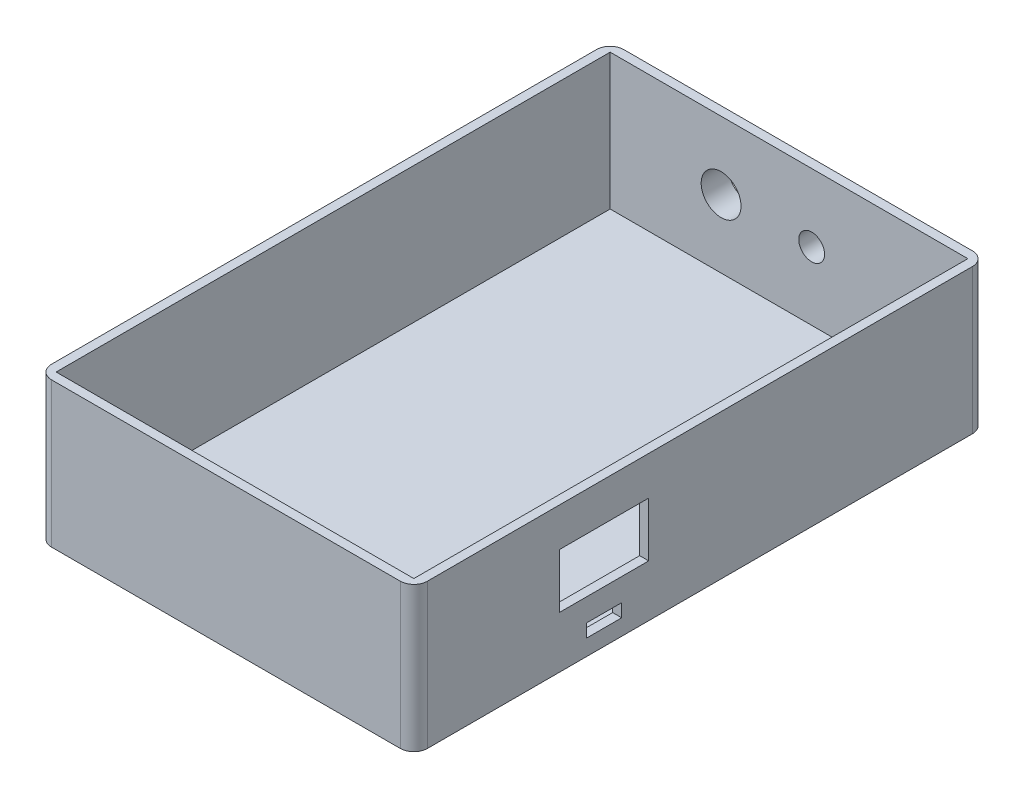
SolidWorks part; units mm, degrees
ref_plane "Front Plane" through (0, 0, 0) normal (0, 0, 1) x (1, 0, 0)
ref_plane "Top Plane" through (0, 0, 0) normal (0, 1, 0) x (1, 0, 0)
ref_plane "Right Plane" through (0, 0, 0) normal (1, 0, 0) x (0, 0, -1)
sketch "Sketch1" plane through (0, 0, 0) normal (0, 1, 0) x (1, 0, 0)
  line L0 (0, 61.175) -> (0, -61.175) construction
  line L1 (-39.5, 61.175) -> (39.5, 61.175)
  line L2 (-39.5, 61.175) -> (-39.5, -61.175)
  line L3 (-39.5, -61.175) -> (39.5, -61.175)
  line L4 (39.5, 61.175) -> (39.5, -61.175)
  line L5 (-41.5, 63.175) -> (-41.5, -63.175)
  line L6 (-41.5, -63.175) -> (41.5, -63.175)
  line L7 (-39, -60.675) -> (-39, -61.175) construction
  line L8 (-28.99, 56.175) -> (28.99, 56.175)
  line L9 (-28.99, 56.175) -> (-28.99, -34.675)
  line L10 (-28.99, -34.675) -> (28.99, -34.675)
  line L11 (28.99, 56.175) -> (28.99, -34.675)
  line L12 (-39, -39.675) -> (39, -39.675)
  line L13 (-39, -39.675) -> (-39, -60.675)
  line L14 (-39, -60.675) -> (39, -60.675)
  line L15 (39, -39.675) -> (39, -60.675)
  line L16 (-39, -60.675) -> (-39.5, -60.675) construction
  line L21 (41.5, 63.175) -> (41.5, -63.175)
  line L22 (-41.5, 63.175) -> (41.5, 63.175)
  point P0 (0, 0)
  point P12 (-28.99, 56.2636)
  point P19 (0, 0)
  point P20 (44, -76.8331)
  point P21 (39, 67.6789)
  point P22 (0, 67.6789)
  point P23 (35.1815, 58.0793)
  point P24 (0, 0)
  point P25 (0, 0)
  point P26 (0, 0)
  point P27 (39, 64.0949)
  dimension "D1" = 90.85
  dimension "D2" = 57.98
  dimension "D3" = 78
  dimension "D4" = 21
  dimension "D5" = 0.5
  dimension "D6" = 5
  dimension "D8" = 2
  dimension "D7" = 5
extrude "Boss-Extrude1" add sketch "Sketch1" along normal blind 2 contours L21 L6 L5 L22
sketch "Sketch2" plane through (0, 2, 0) normal (0, 1, 0) x (1, 0, 0)
  line L4 (39.5, 61.175) -> (-39.5, 61.175)
  line L5 (-39.5, 61.175) -> (-39.5, -61.175)
  line L6 (-39.5, -61.175) -> (39.5, -61.175)
  line L7 (39.5, -61.175) -> (39.5, 61.175)
  line L8 (41.5, 63.175) -> (-41.5, 63.175)
  line L9 (-41.5, 63.175) -> (-41.5, -63.175)
  line L10 (-41.5, -63.175) -> (41.5, -63.175)
  line L11 (41.5, -63.175) -> (41.5, 63.175)
  line L12 (41.5, 63.175) -> (-41.5, 63.175)
  line L13 (-41.5, 63.175) -> (-41.5, -63.175)
  line L14 (-41.5, -63.175) -> (41.5, -63.175)
  line L15 (41.5, -63.175) -> (41.5, 63.175)
  dimension "D1" = 0
  dimension "D2" = 2
extrude "Boss-Extrude2" add sketch "Sketch2" along normal blind 30
sketch "Sketch3" plane through (39.5, 0, 0) normal (-1, 0, 0) x (0, 0, 1)
  line L0 (61.175, 2) -> (-61.175, 2) construction
  line L1 (14.11, 2) -> (28.24, 2) construction
  line L2 (14.11, 2) -> (14.11, 3.54) construction
  line L3 (14.11, 3.54) -> (28.24, 3.54) construction
  line L4 (28.24, 2) -> (28.24, 3.54) construction
  line L5 (21.175, 2) -> (21.175, 17.45) construction
  line L6 (17.275, 3.54) -> (25.075, 3.54)
  line L7 (17.275, 3.54) -> (17.275, 6.44)
  line L8 (17.275, 6.44) -> (25.075, 6.44)
  line L9 (25.075, 3.54) -> (25.075, 6.44)
  line L11 (11.305, 23.46) -> (31.045, 23.46)
  line L12 (11.305, 23.46) -> (11.305, 11.44)
  line L13 (11.305, 11.44) -> (31.045, 11.44)
  line L14 (31.045, 23.46) -> (31.045, 11.44)
  line L15 (11.305, 23.46) -> (31.045, 11.44) construction
  line L16 (11.305, 11.44) -> (31.045, 23.46) construction
  point P12 (21.175, 17.45)
  point P18 (0, 0)
  point P19 (0, 0)
  dimension "D1" = 14.13
  dimension "D2" = 1.54
  dimension "D3" = 2.9
  dimension "D4" = 7.8
  dimension "D5" = 40
  dimension "D6" = 12.02
  dimension "D7" = 19.74
  dimension "D8" = 5
extrude "Cut-Extrude1" cut sketch "Sketch3" against normal through all
sketch "Sketch4" plane through (0, 2, 0) normal (0, 1, 0) x (1, 0, 0)
  line L0 (39.5, -17.275) -> (39.5, -25.075) construction
  line L1 (39.5, -17.275) -> (39.5, -25.075)
  line L2 (39.5, -21.175) -> (31.956, -21.175) construction
  line L4 (39.5, -17.275) -> (24.57, -17.275) construction
  line L5 (39.5, -17.275) -> (39.5, -25.075) construction
  line L6 (39.5, -25.075) -> (24.57, -25.075) construction
  line L7 (24.57, -17.275) -> (24.57, -25.075) construction
  line L8 (24.6, -15.4486) -> (22.4328, -15.4486)
  line L9 (24.6, -15.4486) -> (24.6, -26.9014)
  line L10 (24.6, -26.9014) -> (22.4328, -26.9014)
  line L11 (22.4328, -15.4486) -> (22.4328, -26.9014)
  point P10 (0, 0)
  dimension "D1" = 14.93
extrude "Boss-Extrude3" add sketch "Sketch4" along normal blind 3 contours L8 L11 L10 L9 | L5 L4 L7 L6 region at (23.5164, 2, 21.175)
fillet "Fillet2" radius 3 1 edges at (22.4328, 2, 21.175)
fillet "Fillet1" radius 3 4 edges at (-41.5, 16, -63.175) (41.5, 16, -63.175) (41.5, 16, 63.175) (-41.5, 16, 63.175)
sketch "Sketch6" plane through (0, 0, -61.175) normal (0, 0, 1) x (1, 0, 0)
  line L0 (-39.5, 17) -> (39.5, 17) construction
  line L1 (-39.5, 32) -> (-39.5, 2) construction
  line L2 (39.5, 32) -> (39.5, 2) construction
  line L3 (0, 17) -> (0, 32) construction
  line L4 (39.5, 32) -> (-39.5, 32) construction
  circle A0 centre (-15, 17) radius 4.1 construction
  circle A1 centre (5, 17) radius 2.55 construction
  circle A2 centre (-15, 17) radius 4.4
  circle A3 centre (5, 17) radius 2.85
  dimension "D1" = 8.2
  dimension "D3" = 5.1
  dimension "D5" = 5
  dimension "D6" = 15
  dimension "D2" = 0.3
  dimension "D4" = 0.3
extrude "Cut-Extrude2" cut sketch "Sketch6" against normal through all
sketch "Sketch7" plane through (0, 0, -63.175) normal (0, 0, -1) x (-1, 0, 0)
  line L0 (10.6, 17) -> (-2.15, 17) construction
  line L1 (20.725, 10.5) -> (20.725, 23.5)
  line L2 (21.725, 9.5) -> (-13.275, 9.5)
  line L3 (21.725, 9.5) -> (21.725, 24.5)
  line L4 (21.725, 24.5) -> (-13.275, 24.5)
  line L5 (-13.275, 9.5) -> (-13.275, 24.5)
  line L6 (21.725, 9.5) -> (-13.275, 24.5) construction
  line L7 (21.725, 24.5) -> (-13.275, 9.5) construction
  line L8 (20.725, 23.5) -> (-12.275, 23.5)
  line L9 (-12.275, 10.5) -> (-12.275, 23.5)
  line L10 (20.725, 10.5) -> (-12.275, 10.5)
  circle A0 centre (15, 17) radius 4.4 construction
  circle A1 centre (-5, 17) radius 2.85 construction
  circle A2 centre (-5, 17) radius 2.85
  circle A3 centre (15, 17) radius 4.4
  circle A4 centre (15, 17) radius 5.4
  circle A5 centre (-5, 17) radius 3.85
  point P7 (4.225, 17)
  circle M10 centre (15, 17) radius 4.4
  circle M11 centre (-5, 17) radius 2.85
  dimension "D1" = 35
  dimension "D2" = 15
  dimension "D3" = 1
  dimension "D4" = 1
  dimension "D5" = 1
extrude "Boss-Extrude4" add sketch "Sketch7" along normal blind 2 contours L5 L2 L3 L4 L1 L10 L9 L8 | A4 M10 | A5 M11 region at (-4.225, 9.8808, -63.175) region at (-9.7527, 17, -63.175) region at (8.7411, 17, -63.175)
sketch "Sketch8" plane through (0, 0, -65.175) normal (0, 0, -1) x (-1, 0, 0)
  circle A0 centre (-5, 17) radius 3.85 construction
  circle A1 centre (15, 17) radius 5.4 construction
  circle A2 centre (-5, 17) radius 3.85
  circle A3 centre (15, 17) radius 5.4
  circle A4 centre (15, 17) radius 4.4 construction
  circle A5 centre (15, 17) radius 4.4
  circle A6 centre (-5, 17) radius 2.85 construction
  circle A7 centre (-5, 17) radius 2.85
extrude "Boss-Extrude5" add sketch "Sketch8" along normal blind 2
